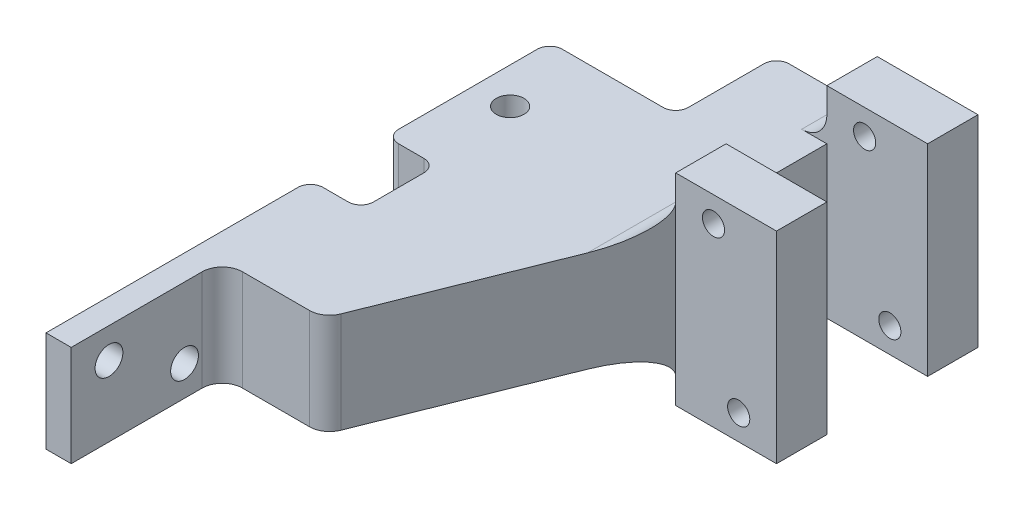
SolidWorks part; units mm, degrees
material "6061-T6 (SS)"
ref_plane "Front Plane" through (0, 0, 0) normal (1, 0, 0) x (0, 1, 0)
ref_plane "Top Plane" through (0, 0, 0) normal (0, 0, 1) x (0, 1, 0)
ref_plane "Right Plane" through (0, 0, 0) normal (0, 1, 0) x (-1, 0, 0)
sketch "Sketch3" plane through (0, 0, 0) normal (0, 1, 0) x (-1, 0, 0)
  line L0 (0, 63.5) -> (0, 0)
  line L1 (0, 63.5) -> (-3.175, 63.5)
  line L4 (-3.175, 63.5) -> (-3.175, 46.99)
  line L7 (0, 0) -> (-28.575, -12.7) construction
  line L8 (-28.575, 6.35) -> (-28.575, -6.35)
  line L9 (-28.575, 12.7) -> (-28.575, -12.7)
  line L10 (-41.275, 6.35) -> (-28.575, 6.35)
  line L11 (-41.275, 6.35) -> (-41.275, -6.35)
  line L12 (-41.275, -6.35) -> (-28.575, -6.35)
  line L13 (-28.575, 6.35) -> (-28.575, -6.35)
  line L14 (-28.575, 12.7) -> (-41.275, 12.7)
  line L16 (-28.575, 6.35) -> (-41.275, 6.35)
  line L17 (-41.275, 12.7) -> (-41.275, 6.35)
  line L18 (-41.275, -6.35) -> (-28.575, -6.35)
  line L19 (-41.275, -6.35) -> (-41.275, -12.7)
  line L20 (-41.275, -12.7) -> (-28.575, -12.7)
  line L22 (0, 0) -> (-14.2875, 0)
  line L23 (0, 30.1625) -> (-6.35, 30.1625)
  line L24 (0, 30.1625) -> (0, 20.6375)
  line L25 (0, 20.6375) -> (-6.35, 20.6375)
  line L26 (-6.35, 30.1625) -> (-6.35, 20.6375)
  line L27 (-5.715, 44.45) -> (-14.1553, 44.45)
  line L28 (-15.875, -1.5875) -> (-15.875, -11.1125)
  line L29 (-17.4625, -12.7) -> (-28.575, -12.7)
  line L30 (-16.5137, 42.8533) -> (-28.575, 12.7)
  arc A0 (-15.875, -11.1125) -> (-17.4625, -12.7) centre (-17.4625, -11.1125) cw
  arc A1 (-15.875, -1.5875) -> (-14.2875, 0) centre (-14.2875, -1.5875) cw
  arc A2 (-3.175, 46.99) -> (-5.715, 44.45) centre (-5.715, 46.99) cw
  arc A3 (-14.1553, 44.45) -> (-16.5137, 42.8533) centre (-14.1553, 41.91) ccw
  point P2 (-28.575, 0)
  point P4 (-28.575, 0)
  point P19 (-6.35, 25.4)
  point P26 (-15.875, 0)
  point P30 (-3.175, 44.45)
  point P33 (-15.875, 44.45)
  dimension "D3" = 19.05
  dimension "D6" = 12.7
  dimension "D13" = 1.5875
  dimension "D15" = 2.54
  dimension "D1" = 3.175
  dimension "D2" = 25.4
  dimension "D4" = 44.45
  dimension "D5" = 28.575
  dimension "D7" = 6.35
  dimension "D8" = 12.7
  dimension "D9" = 25.4
  dimension "D10" = 9.525
  dimension "D11" = 6.35
  dimension "D12" = 15.875
  dimension "D14" = 12.7
extrude "Boss-Extrude1" add sketch "Sketch3" along normal blind 12.7 contours L4 L14 L17 L10 L8 L12 L19 L20 L7 L0 L1 | L28 L7 L29 A0 region at (13.3957, 0, 18.8491) region at (20.1678, 0, -10.7951)
extrude "Boss-Extrude2" add sketch "Sketch3<3>" along normal blind 19.05 and the other way blind 6.35 contours L14 L17 L10 L9 | L19 L20 L9 L12 region at (34.925, 0, 9.525) region at (34.925, 0, -9.525)
sketch "Sketch3<3>" plane through (0, 0, 0) normal (0, 1, 0) x (-1, 0, 0) same geometry as "Sketch3"
fillet "Fillet1" radius 3.175 4 edges at (28.575, 12.7, 9.525) (28.575, 12.7, -9.525) (28.575, 0, -9.525) (28.575, 0, 9.525)
sketch "Sketch4" plane through (0, 0, 12.7) normal (0, 0, 1) x (1, 0, 0)
  line L0 (41.275, -6.35) -> (28.575, -6.35) construction
  line L1 (41.275, 19.05) -> (28.575, 19.05) construction
  line L2 (41.275, -6.35) -> (28.575, -6.35)
  line L3 (41.275, 19.05) -> (28.575, 19.05)
  line L4 (41.275, -6.35) -> (41.275, 19.05) construction
  line L5 (36.5125, -3.175) -> (33.3375, -3.175) construction
  line L6 (36.5125, -3.175) -> (36.5125, 15.875) construction
  line L7 (36.5125, 15.875) -> (33.3375, 15.875) construction
  line L8 (33.3375, -3.175) -> (33.3375, 15.875) construction
  line L9 (36.5125, -3.175) -> (33.3375, 15.875) construction
  line L10 (36.5125, 15.875) -> (33.3375, -3.175) construction
  circle A0 centre (33.3375, 15.875) radius 1.397
  circle A1 centre (36.5125, -3.175) radius 1.397
  point P4 (34.925, 6.35)
  point P11 (41.275, 6.35)
  point P16 (34.925, -6.35)
  dimension "D1" = 2.794
  dimension "D2" = 3.175
  dimension "D3" = 19.05
extrude "Cut-Extrude1" cut sketch "Sketch4" against normal blind 43.18 contours A0 | A1 region at (33.3375, 15.875, 12.7) region at (36.5125, -3.175, 12.7)
sketch "Sketch5" plane through (28.575, 0, 0) normal (1, 0, 0) x (0, 1, 0)
  line L0 (12.7, 6.35) -> (0, -6.35) construction
  line L1 (9.525, 3.175) -> (3.175, -3.175) construction
  circle A0 centre (9.525, 3.175) radius 1.25
  circle A1 centre (3.175, -3.175) radius 1.25
  point P4 (9.525, 3.175)
  point P6 (3.175, -3.175)
  point P8 (6.35, 0)
  point P10 (6.35, 0)
  dimension "D1" = 2.5
  dimension "D2" = 6.35
extrude "Cut-Extrude3" cut sketch "Sketch5" against normal blind 12.7
thread "Thread1" pitch 0.5 method cut profile "Thread Profile1" start angle 0, offset 0, length 0, pitch 0.7937, diameter 2.5
ref_plane "Plane1" through (28.575, 9.525, 4.425) normal (0, -1, 0) x (0, 0, 1)
sketch "Thread Profile1" plane through (28.575, 9.525, 4.425) normal (0, -1, 0) x (0, 0, 1)
  line L0 (0, 0) -> (0, 0.5) construction
  line L1 (0, 0) -> (0.2706, 0.1562)
  line L2 (0.2706, 0.1562) -> (0.2706, 0.2187)
  line L3 (0.2706, 0.2187) -> (0, 0.375)
  line L4 (0.2706, 0.1875) -> (0, 0.1875) construction
  line L11 (0, 0) -> (0, 0.375)
  point P2 (0, 0)
  dimension "Pitch" = 0.5
  dimension "Profile_Angle" = 60
  dimension "Profile_Land" = 0.0625
  dimension "Profile_Height" = 0.2706
thread "Thread2" pitch 0.5 method cut profile "Thread Profile2" start angle 0, offset 0, length 6.35, pitch 0.5, diameter 2.5
ref_plane "Plane2" through (28.575, 3.175, -1.925) normal (0, -1, 0) x (0, 0, 1)
sketch "Thread Profile2" plane through (28.575, 3.175, -1.925) normal (0, -1, 0) x (0, 0, 1)
  line L0 (0, 0) -> (0, 0.5) construction
  line L1 (0, 0) -> (0.2706, 0.1562)
  line L2 (0.2706, 0.1562) -> (0.2706, 0.2187)
  line L3 (0.2706, 0.2187) -> (0, 0.375)
  line L4 (0.2706, 0.1875) -> (0, 0.1875) construction
  line L11 (0, 0) -> (0, 0.375)
  point P2 (0, 0)
  dimension "Pitch" = 0.5
  dimension "Profile_Angle" = 60
  dimension "Profile_Land" = 0.0625
  dimension "Profile_Height" = 0.2706
sketch "Sketch13" plane through (0, 12.7, 0) normal (0, 1, 0) x (-1, 0, 0)
  line L2 (0, 20.6375) -> (0, 0) construction
  circle A0 centre (-4.525, 9.525) radius 1.75
  circle A1 centre (-4.525, 9.525) radius 5 construction
  point P2 (-9.525, 9.525)
  dimension "D2" = 3.5
  dimension "D4" = 10
  dimension "D1" = 9.525
  dimension "D3" = 9.525
extrude "Cut-Extrude4" cut sketch "Sketch13" against normal blind 19.558
sketch "Sketch14" plane through (0, 0, 0) normal (-1, 0, 0) x (0, -1, 0)
  line L8 (-12.7, 0) -> (0, 0) construction
  line L12 (-3.81, 4.7625) -> (-8.89, 4.7625) construction
  line L13 (-3.81, 4.7625) -> (-3.81, 14.2875) construction
  line L14 (-3.81, 14.2875) -> (-8.89, 14.2875) construction
  line L15 (-8.89, 4.7625) -> (-8.89, 14.2875) construction
  line L16 (-3.81, 4.7625) -> (-8.89, 14.2875) construction
  line L17 (-3.81, 14.2875) -> (-8.89, 4.7625) construction
  circle A2 centre (-8.89, 14.2875) radius 1.25
  circle A3 centre (-3.81, 4.7625) radius 1.25
  point P2 (-6.35, 0)
  point P10 (-6.35, 9.525)
  dimension "D1" = 9.525
  dimension "D7" = 2.5
  dimension "D5" = 5.08
  dimension "D6" = 9.525
extrude "Cut-Extrude5" cut sketch "Sketch14" against normal blind 12.7
thread "Thread4" pitch 0.5 method cut profile "Thread Profile4" start angle 0, offset 0, length 10, pitch 0.5, diameter 2.5
ref_plane "Plane4" through (0, 3.81, 3.5125) normal (0, -1, 0) x (0, 0, -1)
sketch "Thread Profile4" plane through (0, 3.81, 3.5125) normal (0, -1, 0) x (0, 0, -1)
  line L0 (0, 0) -> (0, 0.5) construction
  line L1 (0, 0) -> (0.2706, 0.1562)
  line L2 (0.2706, 0.1562) -> (0.2706, 0.2187)
  line L3 (0.2706, 0.2187) -> (0, 0.375)
  line L4 (0.2706, 0.1875) -> (0, 0.1875) construction
  line L11 (0, 0) -> (0, 0.375)
  point P2 (0, 0)
  dimension "Pitch" = 0.5
  dimension "Profile_Angle" = 60
  dimension "Profile_Land" = 0.0625
  dimension "Profile_Height" = 0.2706
sketch "Sketch20" plane through (3.175, 0, 0) normal (1, 0, 0) x (0, 1, 0)
  line L12 (8.89, 49.2125) -> (3.81, 49.2125) construction
  line L13 (8.89, 49.2125) -> (8.89, 58.7375) construction
  line L14 (8.89, 58.7375) -> (3.81, 58.7375) construction
  line L15 (3.81, 49.2125) -> (3.81, 58.7375) construction
  line L16 (8.89, 49.2125) -> (3.81, 58.7375) construction
  line L17 (8.89, 58.7375) -> (3.81, 49.2125) construction
  line L18 (12.7, 63.5) -> (0, 63.5) construction
  circle A6 centre (8.89, 58.7375) radius 1.75
  circle A7 centre (3.81, 49.2125) radius 1.75
  point P0 (6.35, 53.975)
  point P7 (6.35, 63.5)
  dimension "D3" = 3.5
  dimension "D2" = 9.525
  dimension "D1" = 5.08
  dimension "D4" = 53.975
extrude "Cut-Extrude6" cut sketch "Sketch20" against normal blind 22.098 contours A7 | A6 region at (3.175, 8.89, 58.7375) region at (3.175, 3.81, 49.2125)
fillet "Fillet2" radius 1.5875 4 edges at (0, 6.35, 30.1625) (6.35, 6.35, 30.1625) (6.35, 6.35, 20.6375) (0, 6.35, 20.6375)
fillet "Fillet3" radius 1.5875 1 edges at (0, 6.35, 0)
thread "Thread5" pitch 0.5 method cut profile "Thread Profile5" start angle 0, offset 0, length 5, pitch 0.5, diameter 2.5
ref_plane "Plane5" through (0, 8.89, 13.0375) normal (0, -1, 0) x (0, 0, -1)
sketch "Thread Profile5" plane through (0, 8.89, 13.0375) normal (0, -1, 0) x (0, 0, -1)
  line L0 (0, 0) -> (0, 0.5) construction
  line L1 (0, 0) -> (0.2706, 0.1562)
  line L2 (0.2706, 0.1562) -> (0.2706, 0.2187)
  line L3 (0.2706, 0.2187) -> (0, 0.375)
  line L4 (0.2706, 0.1875) -> (0, 0.1875) construction
  line L11 (0, 0) -> (0, 0.375)
  point P2 (0, 0)
  dimension "Pitch" = 0.5
  dimension "Profile_Angle" = 60
  dimension "Profile_Land" = 0.0625
  dimension "Profile_Height" = 0.2706
